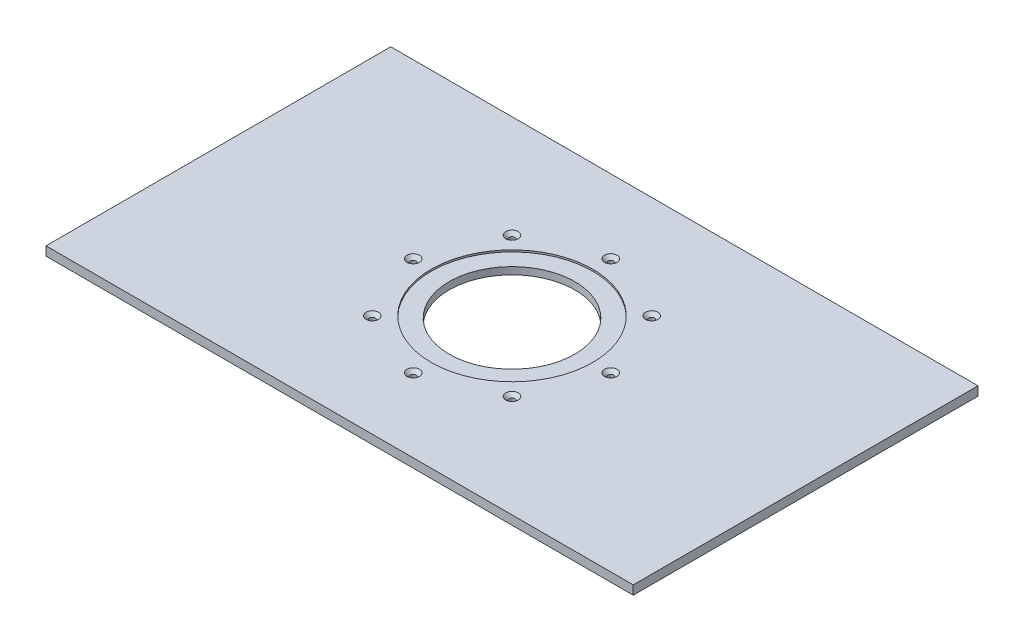
SolidWorks part; units mm, degrees
material "6061-T6 (SS)"
ref_plane "Front Plane" through (0, 0, 0) normal (0, 0, 1) x (1, 0, 0)
ref_plane "Top Plane" through (0, 0, 0) normal (0, 1, 0) x (1, 0, 0)
ref_plane "Right Plane" through (0, 0, 0) normal (1, 0, 0) x (0, 0, -1)
sketch "Sketch1" plane through (0, 0, 0) normal (0, 1, 0) x (1, 0, 0)
  line L1 (-163.5, -96) -> (163.5, -96)
  line L2 (-163.5, -96) -> (-163.5, 96)
  line L3 (-163.5, 96) -> (163.5, 96)
  line L4 (163.5, -96) -> (163.5, 96)
  line L5 (-163.5, -96) -> (163.5, 96) construction
  line L6 (-163.5, 96) -> (163.5, -96) construction
  point P0 (0, 0)
  dimension "D1" = 192
  dimension "D2" = 327
extrude "Boss-Extrude1" add sketch "Sketch1" along normal blind 5
sketch "Sketch2" plane through (0, 5, 0) normal (0, 1, 0) x (1, 0, 0)
  circle A0 centre (0, 0) radius 35
  dimension "D1" = 70
extrude "Cut-Extrude1" cut sketch "Sketch2" against normal through all
sketch "Sketch3" plane through (0, 5, 0) normal (0, 1, 0) x (1, 0, 0)
  circle A0 centre (0, 0) radius 45
  dimension "D1" = 90
extrude "Cut-Extrude2" cut sketch "Sketch3" against normal blind 1
sketch "Sketch6" plane through (0, 5, 0) normal (0, 1, 0) x (1, 0, 0)
  circle A0 centre (0, 0) radius 55
  point P4 (-55, 0)
  point P10 (-38.8909, 38.8909)
  point P11 (0, 55)
  point P12 (38.8909, 38.8909)
  point P13 (55, 0)
  point P14 (38.8909, -38.8909)
  point P15 (0, -55)
  point P16 (-38.8909, -38.8909)
  dimension "D1" = 110
  dimension "D2" = 8
hole_wizard "CSK for M3 Hex Socket Countersunk Head Screw1" positions "Sketch6" profile "Sketch5" countersink size "M3" standard "DIN" end condition through all
sketch "Sketch5" plane through (-38.8909, 5, 38.8909) normal (1, 0, 0) x (0, 0, 1)
  line L0 (0, 0) -> (0, 5)
  line L1 (0, 5) -> (1.6, 5)
  line L2 (1.6, 5) -> (1.6, 1.87)
  line L3 (1.6, 1.87) -> (3.47, 0)
  line L5 (3.47, 0) -> (0, 0)
  line L6 (-1.6, 1.87) -> (-3.47, 0) construction
  line L11 (0, -6.35) -> (0, 107.95) construction
  dimension "Thru Hole Dia." = 3.2
  dimension "Thru Hole Depth" = 5
  dimension "Near C'Sink Dia." = 6.94
  dimension "Near C'Sink Angle" = 90
